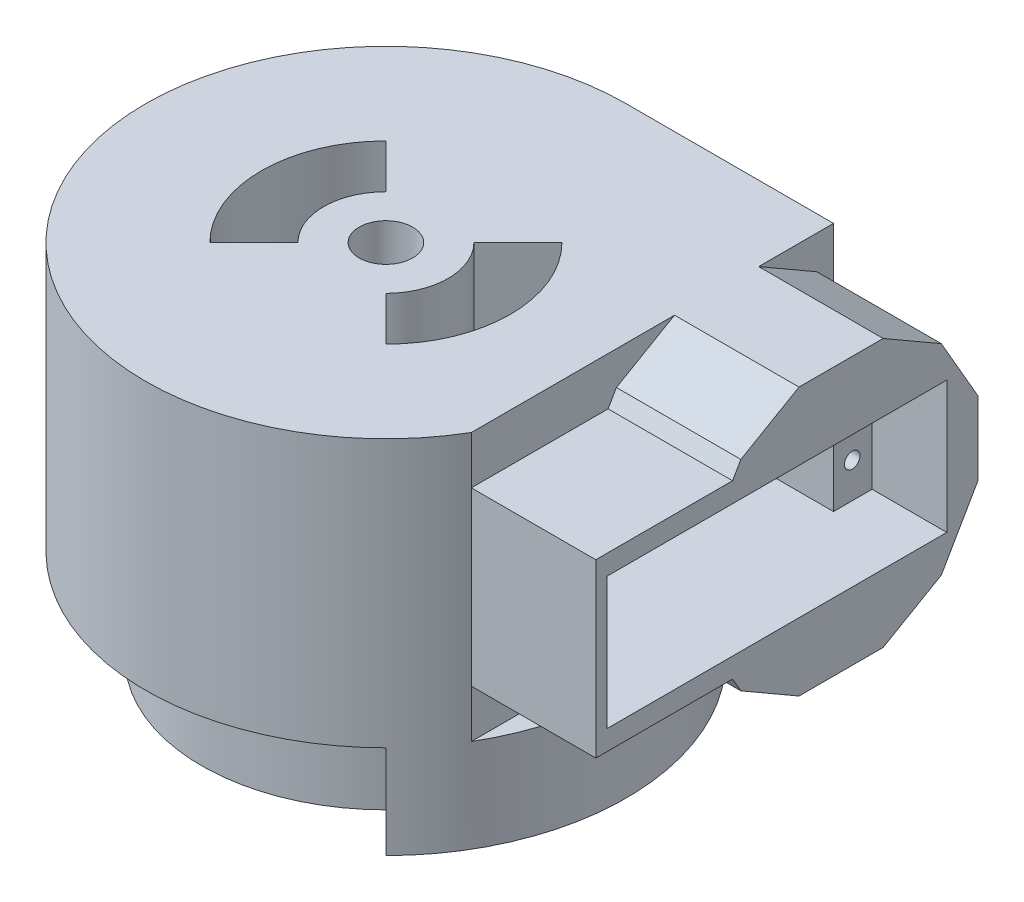
SolidWorks part; units mm, degrees
ref_plane "Front Plane" through (0, 0, 0) normal (0, 0, 1) x (1, 0, 0)
ref_plane "Top Plane" through (0, 0, 0) normal (0, 1, 0) x (1, 0, 0)
ref_plane "Right Plane" through (0, 0, 0) normal (1, 0, 0) x (0, 0, -1)
sketch "Sketch1" plane through (0, 0, 0) normal (0, 1, 0) x (1, 0, 0)
  line L0 (0, 38.625) -> (53.2973, 38.625)
  line L1 (53.2973, 38.625) -> (53.2973, -19.575)
  line L2 (53.2973, -19.575) -> (33.2973, -19.575)
  line L3 (0, 60.3307) -> (0, -56.6529) construction
  arc A0 (0, 38.625) -> (33.2973, -19.575) centre (0, 0) ccw
  dimension "D1" = 20
  dimension "D2" = 38.625
  dimension "D7" = 58.2
extrude "Boss-Extrude1" add sketch "Sketch1" along normal blind 43
sketch "Sketch4" plane through (0, 0, 0) normal (0, -1, 0) x (1, 0, 0)
  line L0 (-38.625, 0) -> (53.2973, 0) construction
  line L1 (53.2973, 19.575) -> (53.2973, -38.625) construction
  line L2 (20.948, 20.948) -> (27.312, 27.312)
  line L3 (20.948, -20.948) -> (27.312, -27.312)
  line L4 (20.948, -20.948) -> (0, 0) construction
  line L5 (0, 0) -> (20.948, 20.948) construction
  arc A0 (33.2973, 19.575) -> (0, -38.625) centre (0, 0) ccw construction
  arc A1 (20.948, 20.948) -> (20.948, -20.948) centre (0, 0) ccw
  arc A4 (27.312, -27.312) -> (27.312, 27.312) centre (0, 0) ccw
  dimension "D1" = 45
  dimension "D2" = 45
  dimension "D3" = 9
extrude "Boss-Extrude2" add sketch "Sketch4" along normal blind 15
sketch "Sketch5" plane through (53.2973, 0, 0) normal (1, 0, 0) x (0, 0, -1)
  line L0 (9.525, 43) -> (9.525, 0) construction
  line L1 (-19.575, 43) -> (38.625, 43) construction
  line L2 (-19.575, 0) -> (38.625, 0) construction
  line L3 (-19.575, 21.5) -> (38.625, 21.5) construction
  line L4 (-19.575, 43) -> (-19.575, 0) construction
  line L5 (38.625, 43) -> (38.625, 0) construction
  line L6 (-14.575, 26.45) -> (-14.575, 16.55) construction
  line L7 (-10.975, 11.5) -> (30.025, 11.5) construction
  line L8 (-10.975, 11.5) -> (-10.975, 31.5) construction
  line L9 (-10.975, 31.5) -> (30.025, 31.5) construction
  line L10 (30.025, 11.5) -> (30.025, 31.5) construction
  line L11 (-10.975, 11.5) -> (30.025, 31.5) construction
  line L12 (-10.975, 31.5) -> (30.025, 11.5) construction
  line L13 (33.625, 26.45) -> (33.625, 16.55) construction
  line L14 (-11.575, 10.9) -> (-11.575, 32.1)
  line L15 (-11.575, 32.1) -> (30.625, 32.1)
  line L16 (30.625, 32.1) -> (30.625, 10.9)
  line L17 (30.625, 10.9) -> (-11.575, 10.9)
  line L18 (-11.575, 10.9) -> (-17.775, 10.9)
  line L19 (-17.775, 10.9) -> (-17.775, 32.1)
  line L20 (-17.775, 32.1) -> (-11.575, 32.1)
  line L21 (30.625, 32.1) -> (36.825, 32.1)
  line L22 (36.825, 32.1) -> (36.825, 10.9)
  line L23 (36.825, 10.9) -> (30.625, 10.9)
  circle A0 centre (-14.575, 26.45) radius 1.25
  circle A1 centre (-14.575, 16.55) radius 1.25
  circle A2 centre (33.625, 16.55) radius 1.25
  circle A3 centre (33.625, 26.45) radius 1.25
  circle A4 centre (19.625, 21.5) radius 6 construction
  point P12 (9.525, 21.5)
  point P25 (-14.575, 21.5)
  point P27 (33.625, 21.5)
  point P38 (9.525, 32.1)
  point P39 (-17.775, 21.5)
  dimension "D8" = 2.5
  dimension "D9" = 2.5
  dimension "D10" = 2.5
  dimension "D11" = 2.5
  dimension "D14" = 12
  dimension "D13" = 17.2
  dimension "D1" = 9.9
  dimension "D2" = 9.9
  dimension "D3" = 24.1
  dimension "D4" = 24.1
  dimension "D5" = 0.6
  dimension "D6" = 20
  dimension "D7" = 54.6
  dimension "D12" = 0.6
  dimension "D15" = 41
extrude "Cut-Extrude1" cut sketch "Sketch5" against normal blind 41 contours L17 L16 L15 L14 region at (53.2973, 21.5, -9.525)
extrude "Cut-Extrude2" cut sketch "Sketch5<5>" against normal blind 12 contours L20 L19 L18 L14 A1 A0 | L23 L22 L21 L16 A3 A2 region at (53.2973, 21.5, 14.6831) region at (53.2973, 21.5, -33.7331)
sketch "Sketch5<5>" plane through (53.2973, 0, 0) normal (1, 0, 0) x (0, 0, -1) same geometry as "Sketch5"
extrude "Cut-Extrude3" cut sketch "Sketch5<6>" against normal blind 35 contours A3 | A2 | A0 | A1 region at (53.2973, 26.45, 14.575) region at (53.2973, 16.55, 14.575) region at (53.2973, 16.55, -33.625) region at (53.2973, 26.45, -33.625)
sketch "Sketch5<6>" plane through (53.2973, 0, 0) normal (1, 0, 0) x (0, 0, -1) same geometry as "Sketch5"
sketch "Sketch6" plane through (0, -15, 0) normal (0, -1, 0) x (1, 0, 0)
  line L0 (0, -38.625) -> (0, 38.625) construction
  line L1 (38.625, 0) -> (-38.625, 0) construction
  line L2 (7.0711, 7.0711) -> (14.1421, 14.1421)
  line L3 (7.0711, -7.0711) -> (14.1421, -14.1421)
  line L4 (0, 0) -> (7.0711, 7.0711) construction
  line L5 (7.0711, -7.0711) -> (0, 0) construction
  line L6 (-7.0711, -7.0711) -> (-14.1421, -14.1421)
  line L7 (-7.0711, 7.0711) -> (-14.1421, 14.1421)
  circle A0 centre (0, 0) radius 4.3
  arc A1 (27.312, 27.312) -> (0, -38.625) centre (0, 0) ccw construction
  arc A2 (27.312, -27.312) -> (27.312, 27.312) centre (0, 0) ccw construction
  arc A3 (7.0711, 7.0711) -> (7.0711, -7.0711) centre (0, 0) cw
  arc A4 (14.1421, -14.1421) -> (14.1421, 14.1421) centre (0, 0) ccw
  arc A5 (-14.1421, -14.1421) -> (-14.1421, 14.1421) centre (0, 0) cw
  arc A6 (-7.0711, 7.0711) -> (-7.0711, -7.0711) centre (0, 0) ccw
  dimension "D1" = 8.6
  dimension "D3" = 10
  dimension "D4" = 10
  dimension "D2" = 45
  dimension "D5" = 45
extrude "Cut-Extrude4" cut sketch "Sketch6" against normal through all both and the other way through all
sketch "Sketch7" plane through (41.2973, 0, 0) normal (1, 0, 0) x (0, 0, -1)
  line L0 (30.625, 32.1) -> (30.625, 10.9) construction
  line L1 (25.625, 18.1) -> (35.625, 18.1)
  line L2 (25.625, 18.1) -> (25.625, 24.9)
  line L3 (25.625, 24.9) -> (35.625, 24.9)
  line L4 (35.625, 18.1) -> (35.625, 24.9)
  line L5 (25.625, 18.1) -> (35.625, 24.9) construction
  line L6 (25.625, 24.9) -> (35.625, 18.1) construction
  point P0 (30.625, 21.5)
  dimension "D1" = 6.8
  dimension "D2" = 10
extrude "Cut-Extrude5" cut sketch "Sketch7" against normal through all from offset 5 offset against normal yes
sketch "Sketch9" plane through (53.2973, 0, 0) normal (1, 0, 0) x (0, 0, -1)
  line L0 (13.9451, 43.5) -> (3.7349, 37.6051)
  line L1 (25.7349, -0.5) -> (35.9451, 5.3949)
  line L2 (35.9451, 5.3949) -> (41.84, 15.6051)
  line L3 (41.84, 15.6051) -> (41.84, 27.3949)
  line L4 (41.84, 27.3949) -> (35.9451, 37.6051)
  line L5 (35.9451, 37.6051) -> (25.7349, 43.5)
  line L6 (25.7349, 43.5) -> (13.9451, 43.5)
  line L7 (3.7349, 37.6051) -> (-2.16, 27.3949)
  line L8 (-2.16, 27.3949) -> (-2.16, 15.6051)
  line L9 (-2.16, 15.6051) -> (3.7349, 5.3949)
  line L10 (3.7349, 5.3949) -> (13.9451, -0.5)
  line L11 (13.9451, -0.5) -> (25.7349, -0.5)
  line L12 (38.625, 43) -> (38.625, 0) construction
  line L13 (-19.575, 43) -> (-19.575, 35.3)
  line L14 (-19.575, 43) -> (-19.575, 0) construction
  line L15 (-19.575, 35.3) -> (2.404, 35.3)
  line L16 (-19.575, 43) -> (13.0791, 43)
  line L17 (26.6009, 43) -> (38.625, 43)
  line L18 (-19.575, 43) -> (38.625, 43) construction
  line L19 (38.625, 43) -> (38.625, 32.9634)
  line L20 (-19.575, 7.7) -> (2.404, 7.7)
  line L21 (-19.575, 7.7) -> (-19.575, 0)
  line L22 (-19.575, 0) -> (13.0791, 0)
  line L23 (-19.575, 0) -> (38.625, 0) construction
  line L24 (-17.775, 32.1) -> (36.825, 32.1) construction
  line L25 (36.825, 10.9) -> (-17.775, 10.9) construction
  line L26 (38.625, 10.0366) -> (38.625, 0)
  line L27 (38.625, 0) -> (26.6009, 0)
  line L28 (38.625, 10.0366) -> (38.625, 32.9634)
  circle A0 centre (19.84, 21.5) radius 22 construction
  line M2 (-19.575, 0) -> (38.625, 0)
  line M3 (38.625, 0) -> (38.625, 43)
  line M4 (38.625, 43) -> (-19.575, 43)
  line M5 (-19.575, 43) -> (-19.575, 0)
  dimension "D1" = 44
  dimension "D2" = 3.2
  dimension "D3" = 3.2
extrude "Cut-Extrude9" cut sketch "Sketch9" against normal up to vertex (20 mm away) contours L5 L4 M3 M4 | L15 L7 L0 M5 M4 | L20 L10 L9 M5 M2 | L2 L1 M2 M3 region at (53.2973, 39.4278, 6.1723) region at (53.2973, 40.2211, -34.8984) region at (53.2973, 3.5722, 6.1723) region at (53.2973, 2.7789, -34.8984) up to point (33.2973, 0, 19.575)
extrude "Boss-Extrude3" add sketch "Sketch9<7>" against normal up to vertex (53.2973 mm away) contours L3 L4 L2 M3 region at (53.2973, 21.5, -40.0606) up to point (0, 43, -38.625)
sketch "Sketch9<7>" plane through (53.2973, 0, 0) normal (1, 0, 0) x (0, 0, -1) same geometry as "Sketch9"
chamfer "Chamfer1" distance 10 angle 45 1 edges at (0, 21.5, -38.625)
